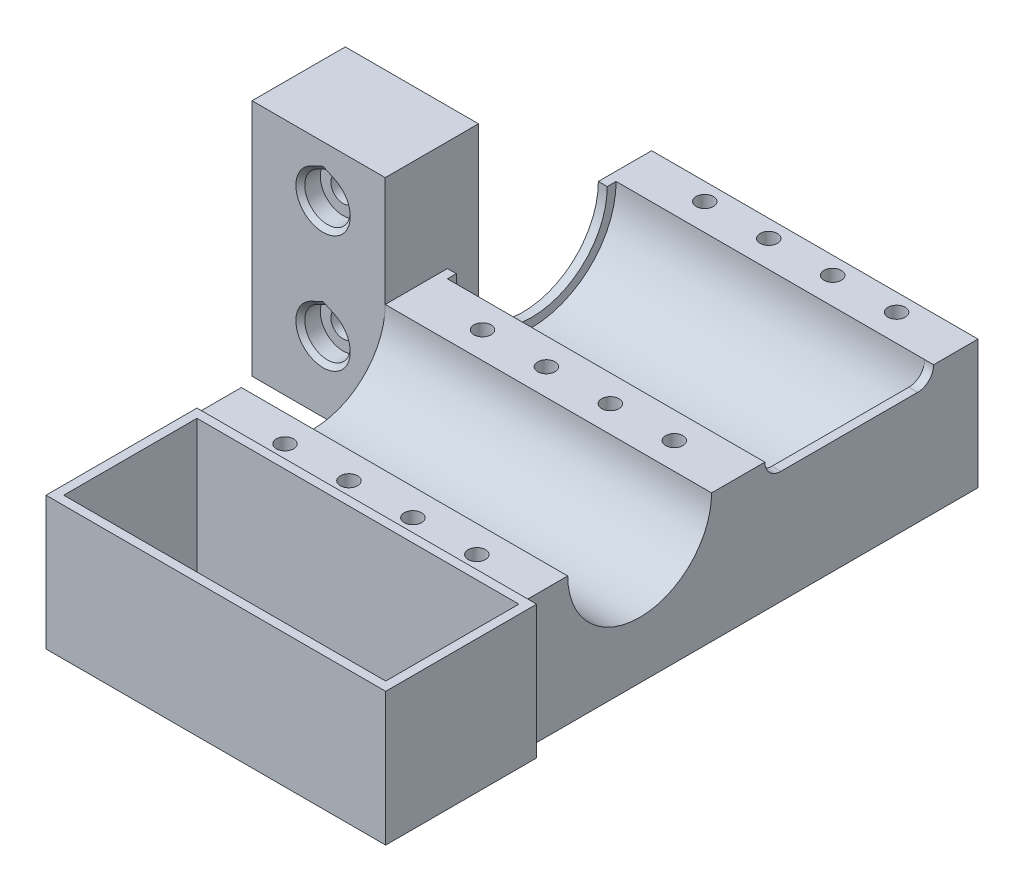
SolidWorks part; units mm, degrees
ref_plane "Front Plane" through (0, 0, 0) normal (0, 0, 1) x (1, 0, 0)
ref_plane "Top Plane" through (0, 0, 0) normal (0, 1, 0) x (1, 0, 0)
ref_plane "Right Plane" through (0, 0, 0) normal (1, 0, 0) x (0, 0, -1)
sketch "Sketch1" plane through (0, 0, 0) normal (1, 0, 0) x (0, 0, -1)
  line L0 (51.2, 42.0261) -> (51.2, 0) construction
  line L1 (0, 0) -> (102.4, 0)
  line L2 (0, 0) -> (0, 29)
  line L3 (102.4, 0) -> (102.4, 29)
  line L4 (0, 29) -> (10, 29) construction
  line L6 (42.4, 29) -> (54.4, 29) construction
  line L7 (42.4, 29) -> (54.4, 29)
  line L8 (0, 29) -> (10, 29)
  line L10 (42.4, 29) -> (54.4, 29)
  line L11 (92.4, 29) -> (102.4, 29)
  arc A0 (10, 29) -> (42.4, 29) centre (26.2, 29) ccw
  arc A1 (54.4, 29) -> (92.4, 29) centre (73.4, 29) ccw
  point P15 (73.4, 10)
  dimension "D3" = 19
  dimension "D4" = 16.2
  dimension "D1" = 10
  dimension "D2" = 12
  dimension "D5" = 10
extrude "Boss-Extrude1" add sketch "Sketch1" along normal blind 73.5 contours L8 L2 L1 L3 L7 region at (0, 11.0871, -50.0531)
sketch "Sketch7" plane through (0, 0, 0) normal (-1, 0, 0) x (0, 0, 1)
  line L0 (0, 0) -> (-102.4, 0) construction
  line L1 (-63.4, 0) -> (-42.4, 0)
  line L2 (-63.4, 0) -> (-63.4, 53.7409)
  line L3 (-63.4, 53.7409) -> (-42.4, 53.7409)
  line L4 (-42.4, 0) -> (-42.4, 53.7409)
  line L5 (-42.4, 29) -> (-54.4, 29) construction
  line L6 (-42.4, 29) -> (-54.4, 29) construction
  arc A0 (-92.4, 29) -> (-54.4, 29) centre (-73.4, 29) ccw construction
  arc A1 (-92.4, 29) -> (-54.4, 29) centre (-73.4, 29) ccw construction
  circle A2 centre (-73.4, 29) radius 6 construction
  dimension "D1" = 12
  dimension "D2" = 10
extrude "Boss-Extrude2" add sketch "Sketch7" along normal blind 30
sketch "Sketch14" plane through (73.5, 0, 0) normal (1, 0, 0) x (0, 0, -1)
  line L0 (54.4, 29) -> (92.4, 29)
  arc A0 (54.4, 29) -> (92.4, 29) centre (73.4, 29) ccw construction
  arc A1 (54.4, 29) -> (92.4, 29) centre (73.4, 29) ccw
extrude "Boss-Extrude3" add sketch "Sketch14" against normal blind 2
sketch "Sketch19" plane through (0, 0, 0) normal (-1, 0, 0) x (0, 0, 1)
  line L1 (-90.4, 29) -> (-92.4, 29)
  line L2 (-56.4, 29) -> (-54.4, 29)
  arc A5 (-63.4, 12.8445) -> (-54.4, 29) centre (-73.4, 29) ccw construction
  arc A7 (-92.4, 29) -> (-63.4, 12.8445) centre (-73.4, 29) ccw construction
  arc A8 (-63.4, 12.8445) -> (-54.4, 29) centre (-73.4, 29) ccw
  arc A9 (-92.4, 29) -> (-63.4, 12.8445) centre (-73.4, 29) ccw
  arc A10 (-90.4, 29) -> (-64.4526, 14.5451) centre (-73.4, 29) ccw
  arc A11 (-64.4526, 14.5451) -> (-56.4, 29) centre (-73.4, 29) ccw
  dimension "D1" = 2
extrude "Boss-Extrude4" add sketch "Sketch19" against normal blind 2
sketch "Sketch26" plane through (0, 0, 0) normal (0, 1, 0) x (1, 0, 0)
  line L0 (2, -2) -> (74.5, -2)
  line L1 (0, 0) -> (76.5, 0)
  line L2 (0, 0) -> (0, -34)
  line L3 (0, -34) -> (76.5, -34)
  line L4 (76.5, 0) -> (76.5, -34)
  line L5 (74.5, -2) -> (74.5, -32)
  line L6 (2, -32) -> (74.5, -32)
  line L7 (2, -2) -> (2, -32)
  dimension "D1" = 34
  dimension "D2" = 76.5
  dimension "D3" = 2
extrude "Boss-Extrude5" add sketch "Sketch26" along normal blind 30
sketch "Sketch8" plane through (0, 0, -63.4) normal (0, 0, -1) x (-1, 0, 0)
  line L0 (30, 53.7409) -> (0, 53.7409) construction
  line L1 (0, 53.7409) -> (0, 15.2523) construction
  line L2 (30, 53.7409) -> (0, 53.7409) construction
  line L3 (0, 53.7409) -> (0, 15.2523) construction
  line L5 (-2, 29) -> (0, 29) construction
  line L6 (12.485, 44.4951) -> (14, 45.4951)
  line L7 (14, 45.4951) -> (15.515, 44.4951)
  line L8 (12.485, 44.4951) -> (15.515, 44.4951) construction
  line L9 (14, 19.0951) -> (12.485, 18.0951)
  line L10 (14, 19.0951) -> (15.515, 18.0951)
  line L11 (15.515, 18.0951) -> (12.485, 18.0951) construction
  line L12 (3.5, 29) -> (45.8321, 29) construction
  line L14 (-2, 29) -> (-2, 10) construction
  line L15 (-2, 29) -> (-2, 10) construction
  line L16 (-2, 29) -> (0, 29) construction
  arc A0 (12.485, 44.4951) -> (15.515, 44.4951) centre (14, 42.2) ccw
  arc A1 (12.485, 18.0951) -> (15.515, 18.0951) centre (14, 15.8) ccw
  dimension "D3" = 5.5
  dimension "D2" = 14
  dimension "D5" = 1
  dimension "D6" = 1
  dimension "D1" = 13.2
  dimension "D4" = 13.2
extrude "Cut-Extrude1" cut sketch "Sketch8" against normal up to surface (21 mm away) up to face at (-12, 27.2964, -42.4)
sketch "Sketch9" plane through (0, 0, -63.4) normal (0, 0, -1) x (-1, 0, 0)
  line L0 (11.8438, 46.8493) -> (14, 47.8493)
  line L1 (14, 47.8493) -> (16.1562, 46.8493)
  line L2 (11.8438, 46.8493) -> (16.1562, 46.8493) construction
  line L3 (11.8438, 20.4493) -> (14, 21.4493)
  line L4 (14, 21.4493) -> (16.1562, 20.4493)
  line L5 (11.8438, 20.4493) -> (16.1562, 20.4493) construction
  arc A0 (11.8438, 46.8493) -> (16.1562, 46.8493) centre (14, 42.2) ccw
  arc A1 (11.8438, 20.4493) -> (16.1562, 20.4493) centre (14, 15.8) ccw
  dimension "D1" = 10.25
  dimension "D2" = 1
  dimension "D3" = 1
extrude "Cut-Extrude2" cut sketch "Sketch9" against normal blind 4.5
sketch "Sketch10" plane through (0, 0, -42.4) normal (0, 0, 1) x (1, 0, 0)
  line L0 (-16.1562, 46.8493) -> (-14, 47.8493)
  line L1 (-14, 47.8493) -> (-11.8438, 46.8493)
  line L2 (-16.1562, 46.8493) -> (-11.8438, 46.8493) construction
  line L3 (-16.1562, 20.4493) -> (-14, 21.4493)
  line L4 (-14, 21.4493) -> (-11.8438, 20.4493)
  line L5 (-16.1562, 20.4493) -> (-11.8438, 20.4493) construction
  arc A0 (-16.1562, 46.8493) -> (-11.8438, 46.8493) centre (-14, 42.2) ccw
  arc A1 (-16.1562, 20.4493) -> (-11.8438, 20.4493) centre (-14, 15.8) ccw
  dimension "D1" = 10.25
  dimension "D2" = 1
  dimension "D3" = 1
extrude "Cut-Extrude8" cut sketch "Sketch10" against normal blind 4.5
sketch "Sketch22" plane through (0, 29, 0) normal (0, 1, 0) x (1, 0, 0)
  line L0 (73.5, 42.4) -> (0, 42.4) construction
  line L1 (71.5, 54.4) -> (2, 54.4) construction
  line L2 (73.5, 42.4) -> (0, 42.4) construction
  line L3 (71.5, 54.4) -> (2, 54.4) construction
  line L4 (36.75, 54.4) -> (36.75, 42.4) construction
  line L5 (36.75, 48.4) -> (1.5, 48.4) construction
  line L6 (36.75, 48.4) -> (73.5, 48.4) construction
  line L7 (73.5, 42.4) -> (73.5, 102.4) construction
  line L8 (73.5, 10) -> (73.5, 42.4) construction
  line L9 (71.5, 92.4) -> (71.5, 54.4) construction
  line L10 (73.5, 10) -> (73.5, 42.4) construction
  line L11 (71.5, 92.4) -> (71.5, 54.4) construction
  line L12 (71.5, 73.4) -> (-4.6102, 73.4) construction
  line L13 (73.5, 26.2) -> (-9.4707, 26.2) construction
  line L14 (6.2217, 98.47) -> (64.0919, 98.47) construction
  line L16 (10.6744, 3.93) -> (59.5979, 3.93) construction
  line L18 (73.5, 102.4) -> (0, 102.4) construction
  line L21 (73.5, 0) -> (0, 0) construction
  circle A0 centre (15.9, 48.4) radius 1.95
  circle A1 centre (30.3, 48.4) radius 1.95
  circle A2 centre (44.7, 48.4) radius 1.95
  circle A3 centre (59.1, 48.4) radius 1.95
  circle A5 centre (59.1, 98.47) radius 1.95
  circle A8 centre (30.3, 98.47) radius 1.95
  circle A9 centre (15.9, 98.47) radius 1.95
  circle A10 centre (44.7, 3.93) radius 1.95
  circle A11 centre (59.1, 3.93) radius 1.95
  circle A14 centre (15.9, 3.93) radius 1.95
  circle A15 centre (44.7, 98.47) radius 1.95
  circle A16 centre (30.3, 3.93) radius 1.95
  dimension "D1" = 3.9
  dimension "D2" = 72
  dimension "D3" = 14.4
  dimension "D4" = 14.4
  dimension "D5" = 14.4
  dimension "D6" = 14.4
  dimension "D7" = 3.93
  dimension "D8" = 3.93
extrude "Cut-Extrude9" cut sketch "Sketch22" against normal up to surface (29 mm away) up to face at (24, 0, -34.84)
sketch "Sketch24" plane through (0, 0, 0) normal (0, -1, 0) x (1, 0, 0)
  line L1 (18.781, -4.9313) -> (18.2076, -1.9357)
  line L2 (18.2076, -1.9357) -> (15.3267, -0.9344)
  line L3 (15.3267, -0.9344) -> (13.019, -2.9287)
  line L4 (13.019, -2.9287) -> (13.5924, -5.9243)
  line L5 (13.5924, -5.9243) -> (16.4733, -6.9256)
  line L6 (16.4733, -6.9256) -> (18.781, -4.9313)
  line L7 (33.1764, -4.9442) -> (32.6165, -1.946)
  line L8 (32.6165, -1.946) -> (29.7401, -0.9318)
  line L9 (29.7401, -0.9318) -> (27.4236, -2.9158)
  line L10 (27.4236, -2.9158) -> (27.9835, -5.914)
  line L11 (27.9835, -5.914) -> (30.8599, -6.9282)
  line L12 (30.8599, -6.9282) -> (33.1764, -4.9442)
  line L13 (47.5773, -4.9416) -> (47.0148, -1.944)
  line L14 (47.0148, -1.944) -> (44.1374, -0.9323)
  line L15 (44.1374, -0.9323) -> (41.8227, -2.9184)
  line L16 (41.8227, -2.9184) -> (42.3852, -5.916)
  line L17 (42.3852, -5.916) -> (45.2626, -6.9277)
  line L18 (45.2626, -6.9277) -> (47.5773, -4.9416)
  line L19 (61.978, -4.9397) -> (61.4134, -1.9424)
  line L20 (61.4134, -1.9424) -> (58.5354, -0.9327)
  line L21 (58.5354, -0.9327) -> (56.222, -2.9203)
  line L22 (56.222, -2.9203) -> (56.7866, -5.9176)
  line L23 (56.7866, -5.9176) -> (59.6646, -6.9273)
  line L24 (59.6646, -6.9273) -> (61.978, -4.9397)
  line L25 (62.0926, -48.9887) -> (61.1062, -46.1027)
  line L26 (61.1062, -46.1027) -> (58.1135, -45.5139)
  line L27 (58.1135, -45.5139) -> (56.1074, -47.8113)
  line L28 (56.1074, -47.8113) -> (57.0938, -50.6973)
  line L29 (57.0938, -50.6973) -> (60.0865, -51.2861)
  line L30 (60.0865, -51.2861) -> (62.0926, -48.9887)
  line L31 (47.6946, -48.9785) -> (46.6983, -46.0959)
  line L32 (46.6983, -46.0959) -> (43.7037, -45.5173)
  line L33 (43.7037, -45.5173) -> (41.7054, -47.8215)
  line L34 (41.7054, -47.8215) -> (42.7017, -50.7041)
  line L35 (42.7017, -50.7041) -> (45.6963, -51.2827)
  line L36 (45.6963, -51.2827) -> (47.6946, -48.9785)
  line L37 (33.2885, -49.0095) -> (32.3221, -46.1167)
  line L38 (32.3221, -46.1167) -> (29.3336, -45.5071)
  line L39 (29.3336, -45.5071) -> (27.3115, -47.7905)
  line L40 (27.3115, -47.7905) -> (28.2779, -50.6833)
  line L41 (28.2779, -50.6833) -> (31.2664, -51.2929)
  line L42 (31.2664, -51.2929) -> (33.2885, -49.0095)
  line L43 (18.884, -49.0308) -> (17.9384, -46.1312)
  line L44 (17.9384, -46.1312) -> (14.9543, -45.5003)
  line L45 (14.9543, -45.5003) -> (12.916, -47.7692)
  line L46 (12.916, -47.7692) -> (13.8616, -50.6688)
  line L47 (13.8616, -50.6688) -> (16.8457, -51.2997)
  line L48 (16.8457, -51.2997) -> (18.884, -49.0308)
  line L49 (15.8854, -95.42) -> (13.2513, -96.9577)
  line L50 (13.2513, -96.9577) -> (13.266, -100.0077)
  line L51 (13.266, -100.0077) -> (15.9146, -101.52)
  line L52 (15.9146, -101.52) -> (18.5487, -99.9823)
  line L53 (18.5487, -99.9823) -> (18.534, -96.9323)
  line L54 (18.534, -96.9323) -> (15.8854, -95.42)
  line L55 (30.2854, -95.42) -> (27.6514, -96.9577)
  line L56 (27.6514, -96.9577) -> (27.666, -100.0076)
  line L57 (27.666, -100.0076) -> (30.3146, -101.52)
  line L58 (30.3146, -101.52) -> (32.9486, -99.9823)
  line L59 (32.9486, -99.9823) -> (32.934, -96.9324)
  line L60 (32.934, -96.9324) -> (30.2854, -95.42)
  line L61 (44.6853, -95.42) -> (42.0513, -96.9577)
  line L62 (42.0513, -96.9577) -> (42.066, -100.0077)
  line L63 (42.066, -100.0077) -> (44.7147, -101.52)
  line L64 (44.7147, -101.52) -> (47.3487, -99.9823)
  line L65 (47.3487, -99.9823) -> (47.334, -96.9323)
  line L66 (47.334, -96.9323) -> (44.6853, -95.42)
  line L67 (59.0854, -95.42) -> (56.4513, -96.9577)
  line L68 (56.4513, -96.9577) -> (56.466, -100.0077)
  line L69 (56.466, -100.0077) -> (59.1146, -101.52)
  line L70 (59.1146, -101.52) -> (61.7487, -99.9823)
  line L71 (61.7487, -99.9823) -> (61.734, -96.9323)
  line L72 (61.734, -96.9323) -> (59.0854, -95.42)
  circle A0 centre (15.9, -3.93) radius 2.6414 construction
  circle A1 centre (30.3, -3.93) radius 2.6414 construction
  circle A2 centre (44.7, -3.93) radius 2.6414 construction
  circle A3 centre (59.1, -3.93) radius 2.6414 construction
  circle A4 centre (59.1, -48.4) radius 2.6414 construction
  circle A5 centre (44.7, -48.4) radius 2.6414 construction
  circle A6 centre (30.3, -48.4) radius 2.6414 construction
  circle A7 centre (15.9, -48.4) radius 2.6414 construction
  circle A8 centre (15.9, -98.47) radius 2.6414 construction
  circle A9 centre (30.3, -98.47) radius 2.6414 construction
  circle A10 centre (44.7, -98.47) radius 2.6414 construction
  circle A11 centre (59.1, -98.47) radius 2.6414 construction
  dimension "D1" = 6.1
extrude "Cut-Extrude10" cut sketch "Sketch24" against normal blind 3
sketch "Sketch25" plane through (73.5, 0, 0) normal (1, 0, 0) x (0, 0, -1)
  line L0 (57.993, 29) -> (88.807, 29) construction
  line L1 (42.4, 29) -> (102.4, 29) construction
  line L2 (57.993, 32.593) -> (88.807, 32.593)
  line L3 (57.993, 25.407) -> (88.807, 25.407)
  line L6 (92.4, 29) -> (54.4, 29) construction
  line L7 (92.4, 29) -> (54.4, 29) construction
  arc A0 (57.993, 32.593) -> (57.993, 25.407) centre (57.993, 29) ccw
  arc A1 (88.807, 25.407) -> (88.807, 32.593) centre (88.807, 29) ccw
  point P5 (73.4, 29)
  point P12 (92.4, 29)
extrude "Cut-Extrue11" cut sketch "Sketch25" against normal blind 2
chamfer "Chamfer1" distance 1 angle 45 12 edges at (-15.0781, 20.9493, -42.4) (-12.9219, 20.9493, -42.4) (-14, 10.675, -42.4) (-15.0781, 47.3493, -42.4) (-12.9219, 47.3493, -42.4) (-14, 37.075, -42.4) (-12.9219, 20.9493, -63.4) (-15.0781, 20.9493, -63.4) (-14, 10.675, -63.4) (-12.9219, 47.3493, -63.4) (-15.0781, 47.3493, -63.4) (-14, 37.075, -63.4)
equation "\"MotorDIA\"= 37'ME 405 Motor Diameter"
equation "\"SyringeDIA\"= 31.4'60ml Syringe Diameter"
equation "\"MotorShaftDIA\"= 6'Motor Shaft Dia"
equation "\"MotorKeyway\"= 1'ME 405 Motor Shaft Keyway Depth"
equation "\"MotorLength\"= 67.5'ME 405 Motor Length Excluding Shaft"
equation "\"SyringeLength\"= 117.3'60ml Syringe Length Excluding Nozzle"
equation "\"3Dtol\"= .5'Sizing Tolerance for 3D printed parts"
equation "\"ChamberDIA\"= 100 - 4'Buoyancy Chamber inner Diameter"
equation "\"ChamberThk\"= 2mm'Buoyancy Chamber Wall Thickness"
equation "\"D4@Sketch1\"=\"SyringeDIA\"/2+\"3Dtol\""
equation "\"D3@Sketch1\"=\"MotorDIA\"/2+\"3Dtol\""
equation "\"D1@Boss-Extrude1\"=\"MotorLength\"+4*\"3Dtol\"+4mm"
equation "\"D3@Sketch22\"=\"D2@Sketch22\"/5"
equation "\"D4@Sketch22\"=\"D3@Sketch22\""
equation "\"D5@Sketch22\"=\"D3@Sketch22\""
equation "\"D6@Sketch22\"=\"D3@Sketch22\""
equation "\"D4@Sketch8\"=\"D1@Sketch8\""
equation "\"BearingOD\"= 10"
equation "\"BearingID\"= 4"
equation "\"Bearingwidth\"= 4"
equation "\"ShaftDIA\"= 4"
